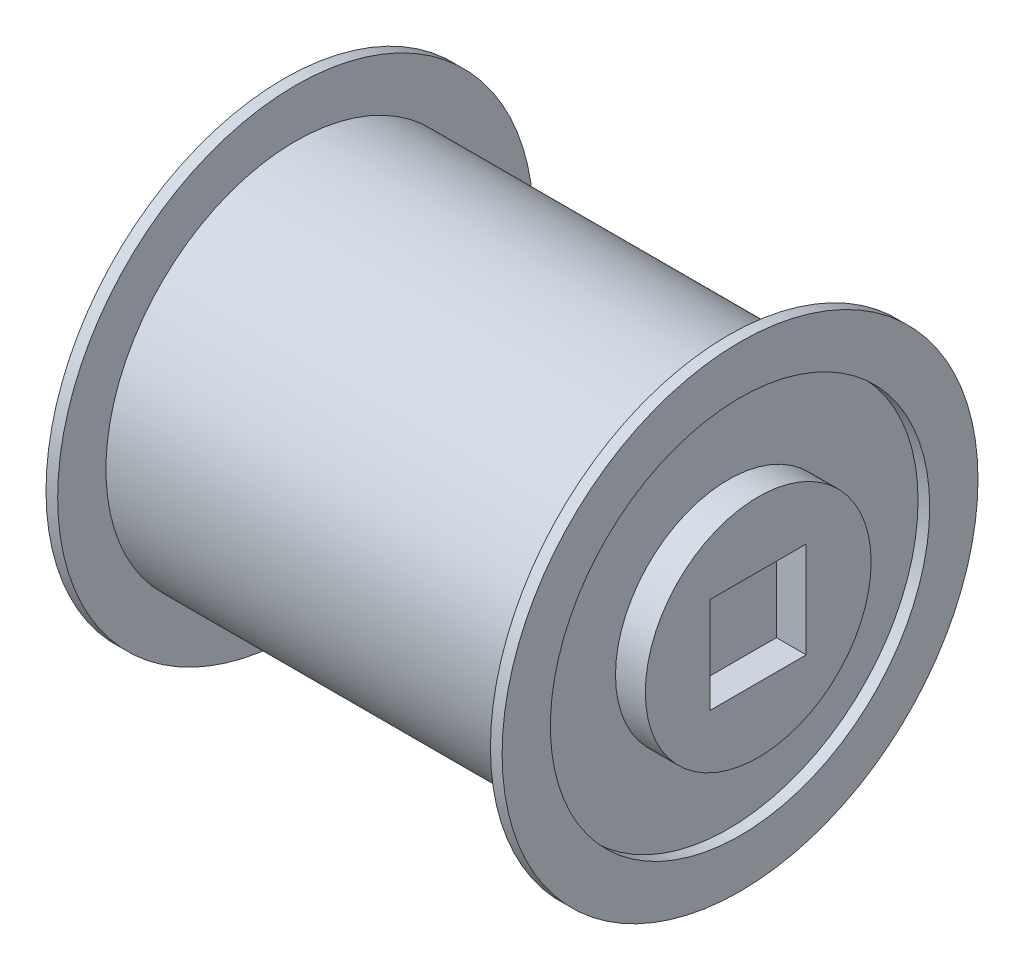
SolidWorks part; units mm, degrees
ref_plane "Front Plane" through (0, 0, 0) normal (0, 0, 1) x (1, 0, 0)
ref_plane "Top Plane" through (0, 0, 0) normal (0, 1, 0) x (1, 0, 0)
ref_plane "Right Plane" through (0, 0, 0) normal (1, 0, 0) x (0, 0, -1)
sketch "Sketch12" plane through (0, 0, 0) normal (1, 0, 0) x (0, 0, -1)
  line L1 (4.1203, 4.1203) -> (4.1203, -4.1203)
  line L2 (4.1203, 4.1203) -> (-4.1203, 4.1203)
  line L3 (-4.1203, 4.1203) -> (-4.1203, -4.1203)
  line L4 (4.1203, -4.1203) -> (-4.1203, -4.1203)
  line L5 (4.1203, 4.1203) -> (-4.1203, -4.1203) construction
  line L6 (-4.1203, 4.1203) -> (4.1203, -4.1203) construction
  circle A0 centre (0, 0) radius 9.6922
  circle A1 centre (0, 0) radius 16.28
  circle A2 centre (0, 0) radius 20.425
  dimension "D1" = 32.56
  dimension "D2" = 40.85
extrude "Boss-Extrude3" add sketch "Sketch12" against normal blind 2.56 and the other way blind 39.71 contours A0 | L1 L4 L3 L2
extrude "Boss-Extrude4" add sketch "Sketch12<9>" against normal blind 1 separate body contours A2 | A1
sketch "Sketch12<9>" plane through (0, 0, 0) normal (1, 0, 0) x (0, 0, -1) same geometry as "Sketch12"
extrude "Boss-Extrude6" add sketch "Sketch12<11>" along normal blind 37.15 contours L2 L3 L4 L1 | A0 | A1
sketch "Sketch12<11>" plane through (0, 0, 0) normal (1, 0, 0) x (0, 0, -1) same geometry as "Sketch12"
ref_axis "Axis4" through (37.15, 0, 0) along (-1, 0, 0)
pattern_linear "LPattern1" count 2 spacing 38.15 along (1, 0, 0) of "Boss-Extrude4"
